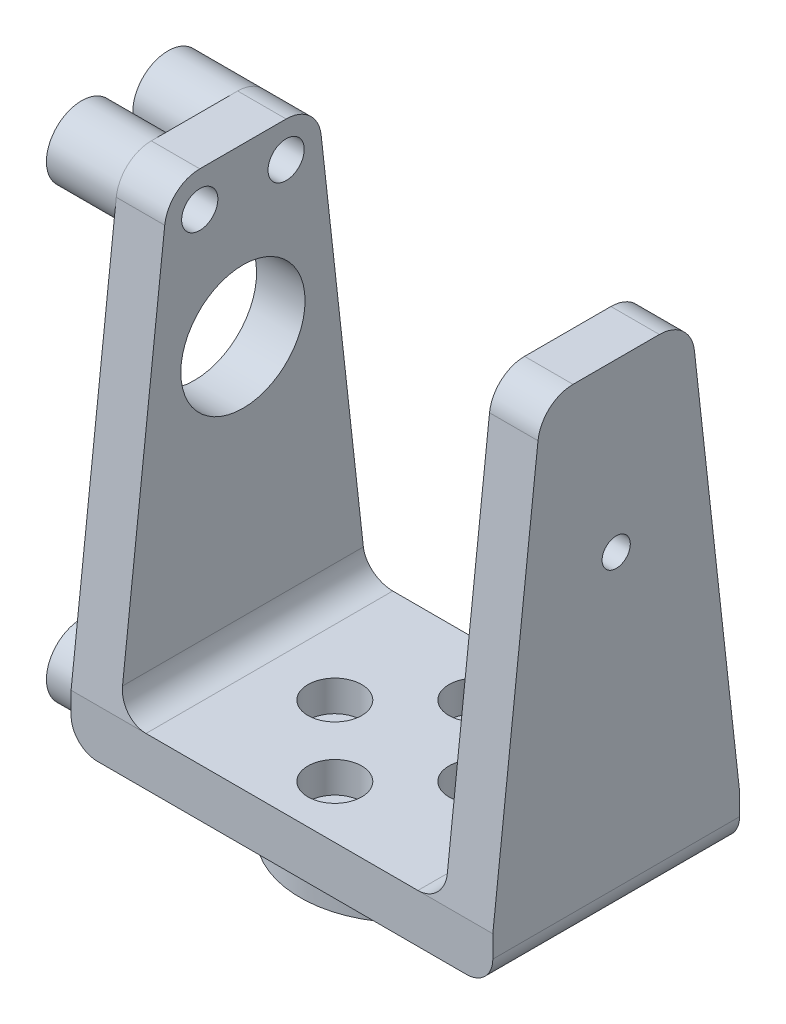
SolidWorks part; units mm, degrees
ref_plane "Front Plane" through (0, 0, 0) normal (0, 0, 1) x (1, 0, 0)
ref_plane "Top Plane" through (0, 0, 0) normal (0, 1, 0) x (1, 0, 0)
ref_plane "Right Plane" through (0, 0, 0) normal (1, 0, 0) x (0, 0, -1)
sketch "Sketch6" plane through (0, 0, 0) normal (0, 0, 1) x (1, 0, 0)
  line L0 (0, 0) -> (-14, 0)
  line L2 (-23.9289, 9.9289) -> (-23.9289, 60)
  line L3 (-23.9289, 60) -> (-18.4289, 60)
  line L4 (-18.4289, 60) -> (-18.4289, 12)
  line L6 (-11.9289, 5.5) -> (0, 5.5)
  line L7 (0, 5.5) -> (0, 0)
  line L8 (-14, 0) -> (-23.9289, 0)
  line L9 (-23.9289, 0) -> (-23.9289, 9.9289)
  line L10 (-18.4289, 12) -> (-18.4289, 5.5)
  line L11 (-18.4289, 5.5) -> (-11.9289, 5.5)
  dimension "D1" = 5.5
  dimension "D2" = 60
  dimension "D3" = 14
  dimension "D4" = 23.9289
  dimension "D5" = 48
  dimension "D6" = 50.0711
  dimension "D7" = 11.9289
extrude "Gimbal Mount Body" add sketch "Sketch6" against normal blind 28
mirror "Gimbal Mount Body Mirror" about plane through (0, 0, 0) normal (1, 0, 0) of "Gimbal Mount Body"
sketch "Sketch7" plane through (-23.9289, 0, 0) normal (-1, 0, 0) x (0, 0, 1)
  line L2 (-14, 12) -> (-14, 60) construction
  line L3 (-28, 60) -> (0, 60) construction
  circle A0 centre (-14, 36) radius 7.05
  dimension "D1" = 14.1
  dimension "D2" = 48
extrude "Servo Gear Mound Cut Out" cut sketch "Sketch7" against normal up to surface (5.5 mm away) up to face at (-18.4289, 32.75, -14)
sketch "Servo Mounting Pattern Reference Sketch2" plane through (-23.9289, 0, 0) normal (-1, 0, 0) x (0, 0, 1)
  line L0 (-14, 36) -> (-14, 50.94) construction
  line L1 (-14, 36) -> (-14, 0.06) construction
  line L2 (-18.9, 50.94) -> (-9.1, 50.94) construction
  line L3 (-18.9, 0.06) -> (-9.1, 0.06) construction
  circle A0 centre (-18.9, 50.94) radius 2.15 construction
  circle A1 centre (-9.1, 50.94) radius 2.15 construction
  circle A2 centre (-18.9, 0.06) radius 2.15 construction
  circle A3 centre (-9.1, 0.06) radius 2.15 construction
  point P9 (-14, 0.06)
  point P11 (-14, 50.94)
  dimension "D5" = 4.3
  dimension "D1" = 9.8
  dimension "D2" = 9.8
  dimension "D3" = 14.94
  dimension "D4" = 35.94
sketch "Sketch14" plane through (-23.9289, 0, 0) normal (-1, 0, 0) x (0, 0, 1)
  line L17 (-18.9, -3.94) -> (-9.1, -3.94)
  line L20 (-28, 0) -> (0, 0) construction
  line L21 (-22.8995, 0) -> (-5.1005, 0)
  arc A6 (-22.8995, 0) -> (-18.9, -3.94) centre (-18.9, 0.06) ccw
  arc A7 (-9.1, -3.94) -> (-5.1005, 0) centre (-9.1, 0.06) ccw
  dimension "D1" = 4
extrude "Boss-Extrude6" add sketch "Sketch14" against normal up to surface (5.5 mm away) up to face at (-18.4289, 43.05, -14)
sketch "Sketch15" plane through (-23.9289, 0, 0) normal (-1, 0, 0) x (0, 0, 1)
  circle A0 centre (-18.9, 50.94) radius 4
  circle A1 centre (-9.1, 50.94) radius 4
  circle A2 centre (-18.9, 0.06) radius 4
  circle A3 centre (-9.1, 0.06) radius 4
  dimension "D1" = 8
extrude "Boss-Extrude7" add sketch "Sketch15" along normal blind 7.9
sketch "Sketch17" plane through (23.9289, 0, 0) normal (1, 0, 0) x (0, 0, -1)
  circle A0 centre (14, 36) radius 1.6
  circle A1 centre (14, 36) radius 7.05 construction
  circle A2 centre (14, 36) radius 7.05 construction
  dimension "D1" = 3.2
extrude "Cut-Extrude2" cut sketch "Sketch17" against normal up to surface (5.5 mm away) up to face at (18.4289, 32.75, -14)
sketch "Sketch19" plane through (0, 0, 0) normal (0, -1, 0) x (1, 0, 0)
  line L6 (0, 0) -> (0, -28) construction
  line L7 (-23.9289, -28) -> (23.9289, -28) construction
  circle A0 centre (0, -14) radius 11.95
  dimension "D1" = 23.9
extrude "Boss-Extrude9" add sketch "Sketch19" along normal up to surface (3.94 mm away) up to face at (-21.1789, -3.94, -14)
sketch "Sketch20" plane through (0, -3.94, 0) normal (0, -1, 0) x (1, 0, 0)
  line L0 (-8, -14) -> (8, -14) construction
  line L1 (0, -6) -> (0, -22) construction
  circle A0 centre (0, -6) radius 1.75
  circle A1 centre (-8, -14) radius 1.75
  circle A2 centre (8, -14) radius 1.75
  circle A3 centre (0, -22) radius 1.75
  point P0 (0, -14)
  point P5 (0, -14)
  point P7 (0, -14)
  dimension "D3" = 3.5
  dimension "D1" = 16
  dimension "D2" = 16
extrude "Cut-Extrude4" cut sketch "Sketch20" against normal up to surface (9.44 mm away) up to face at (0, 5.5, -14)
sketch "Sketch21" plane through (-31.8289, 0, 0) normal (-1, 0, 0) x (0, 0, 1)
  circle A0 centre (-18.9, 50.94) radius 2.055
  circle A1 centre (-9.1, 50.94) radius 2.055
  circle A2 centre (-9.1, 0.06) radius 2.055
  circle A3 centre (-18.9, 0.06) radius 2.055
  dimension "D1" = 4.11
extrude "Cut-Extrude5" cut sketch "Sketch21" against normal up to surface (13.4 mm away) up to face at (-18.4289, 43.05, -14)
sketch "Sketch30" plane through (18.4289, 0, 0) normal (-1, 0, 0) x (0, 0, 1)
  circle A0 centre (-14, 36) radius 1.6
  circle A1 centre (-14, 36) radius 1.6 construction
  circle A2 centre (-14, 36) radius 2.3
  dimension "D1" = 4.6
extrude "Boss-Extrude10" add sketch "Sketch30" along normal blind 0.5
sketch "Sketch22" plane through (23.9289, 0, 0) normal (1, 0, 0) x (0, 0, -1)
  circle A0 centre (14, 36) radius 3.75
  dimension "D1" = 7.5
extrude "Cut-Extrude6" [suppressed] cut sketch "Sketch22" against normal blind 1
sketch "Sketch24" [suppressed] plane through (18.4289, 0, 0) normal (-1, 0, 0) x (0, 0, 1)
  circle A0 centre (-14, 36) radius 3.75 construction
  circle A1 centre (-14, 36) radius 3.75
extrude "Cut-Extrude8" [suppressed] cut sketch "Sketch24" against normal blind 3.1
sketch "Sketch25" [suppressed] plane through (22.9289, 0, 0) normal (1, 0, 0) x (0, 0, -1)
  circle A0 centre (14, 36) radius 3.25
  circle A2 centre (14, 36) radius 3.75 construction
  circle A3 centre (14, 36) radius 3.75
  circle M4 centre (14, 36) radius 1.75
  dimension "D1" = 6.5
extrude "Cut-Extrude9" [suppressed] cut sketch "Sketch25" against normal blind 0.25 contours A0 M4
sketch "Sketch26" [suppressed] plane through (21.5289, 0, 0) normal (-1, 0, 0) x (0, 0, 1)
  circle A0 centre (-14, 36) radius 3.25
  circle A2 centre (-14, 36) radius 3.75 construction
  circle A3 centre (-14, 36) radius 3.75
  circle M5 centre (-14, 36) radius 1.75
  dimension "D1" = 6.5
extrude "Cut-Extrude10" [suppressed] cut sketch "Sketch26" against normal blind 0.25 contours A0 M5
sketch "Sketch28" plane through (-23.9289, 0, 0) normal (-1, 0, 0) x (0, 0, 1)
  line L0 (-28, 5.5) -> (0, 5.5) construction
  line L1 (-28, 5.5) -> (0, 5.5) construction
  line L2 (0, 5.5) -> (-6.087, 60)
  line L3 (-28, 60) -> (0, 60) construction
  line L4 (-28, 5.5) -> (-21.913, 60)
  line L5 (-6.087, 60) -> (0, 60)
  line L6 (0, 60) -> (0, 5.5)
  line L7 (-21.913, 60) -> (-28, 60)
  line L8 (-28, 60) -> (-28, 5.5)
  circle A0 centre (-9.1, 50.94) radius 4 construction
  circle A1 centre (-18.9, 50.94) radius 4 construction
extrude "Cut-Extrude11" cut sketch "Sketch28" against normal through all
sketch "Sketch29" plane through (0, 5.5, 0) normal (0, 1, 0) x (1, 0, 0)
  circle A0 centre (0, 22) radius 3.05
  circle A1 centre (-8, 14) radius 3.05
  circle A2 centre (0, 6) radius 3.05
  circle A3 centre (8, 14) radius 3.05
  dimension "D1" = 6.1
extrude "Cut-Extrude12" cut sketch "Sketch29" against normal blind 3.5
sketch "Sketch23" plane through (-23.9289, 0, 0) normal (-1, 0, 0) x (0, 0, 1)
  line L1 (-21.913, 60) -> (-6.087, 60)
  line L2 (-21.913, 60) -> (-22.4781, 54.94)
  line L3 (-22.4781, 54.94) -> (-5.5219, 54.94)
  line L4 (-6.087, 60) -> (-5.5219, 54.94)
  line L5 (-22.8753, 51.384) -> (-21.913, 60) construction
  line L6 (-6.087, 60) -> (-5.1247, 51.384) construction
  circle A0 centre (-9.1, 50.94) radius 4 construction
extrude "Cut-Extrude7" cut sketch "Sketch23" against normal through all
fillet "Fillet4" radius 3 5 edges at (-23.9289, 0, -2.5502) (-23.9289, 0, -25.4498) (23.9289, 0, -14) (-18.4289, 5.5, -14) (18.4289, 5.5, -14)
fillet "Fillet5" radius 4 4 edges at (21.1789, 54.94, -5.5219) (21.1789, 54.94, -22.4781) (-21.1789, 54.94, -22.4781) (-21.1789, 54.94, -5.5219)
